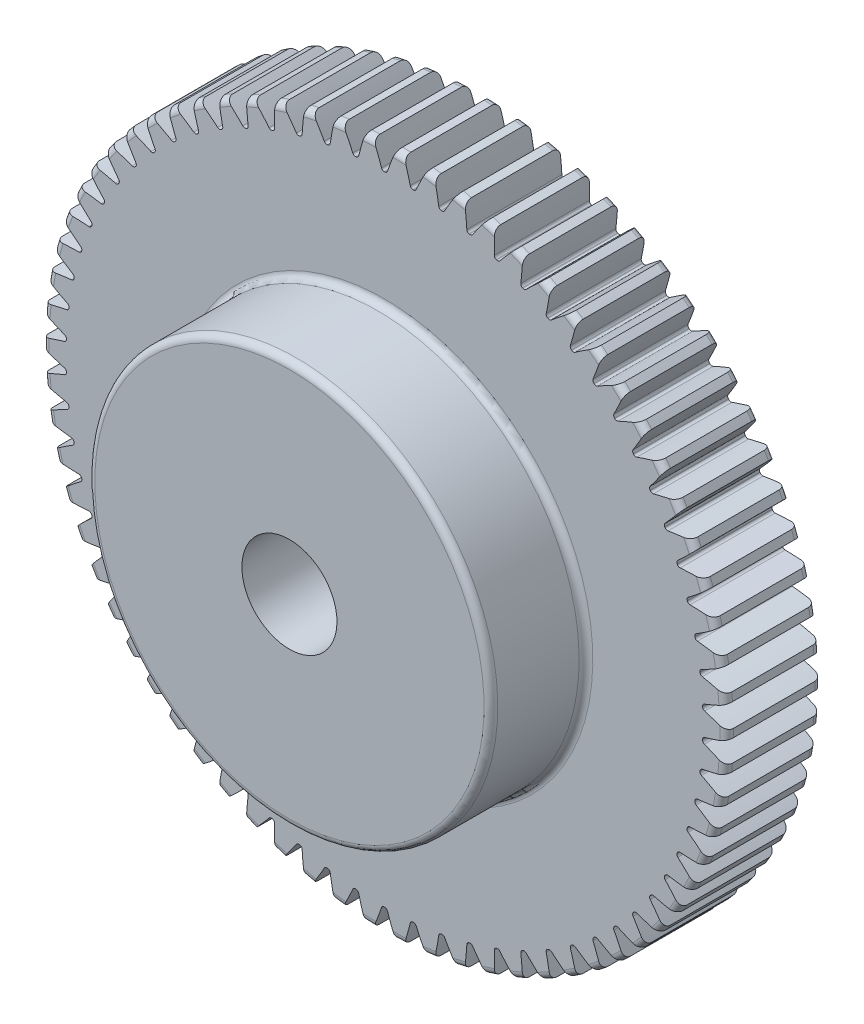
SolidWorks part; units mm, degrees
ref_plane "Front Plane" through (0, 0, 0) normal (0, 0, 1) x (1, 0, 0)
ref_plane "Top Plane" through (0, 0, 0) normal (0, 1, 0) x (1, 0, 0)
ref_plane "Right Plane" through (0, 0, 0) normal (1, 0, 0) x (0, 0, -1)
sketch "Sketch1" plane through (0, 0, 0) normal (0, 0, 1) x (1, 0, 0)
  line L0 (-889, 0) -> (889, 0) construction
  circle A0 centre (0, 0) radius 45.72 construction
  circle A1 centre (0, 0) radius 44.45 construction
  circle A2 centre (0, 0) radius 42.545 construction
  circle A3 centre (0, 0) radius 26.924 construction
  circle A4 centre (0, 0) radius 6.35 construction
  dimension "D2" = 1.27
  dimension "D3" = 3.175
  dimension "D1" = 3.175
sketch "Sketch2" plane through (0, 0, 0) normal (1, 0, 0) x (0, 0, -1)
  line L0 (0, 0) -> (-12.7, 0) construction
  line L1 (-12.7, 0) -> (-25.4, 0) construction
  dimension "Overall Width" = 25.4
  dimension "Face Width" = 12.7
sketch "Sketch4" plane through (0, 0, 0) normal (1, 0, 0) x (0, 0, -1)
  line L0 (-25.4, 6.35) -> (-25.4, 26.924)
  line L1 (-25.4, 26.924) -> (-12.7, 26.924)
  line L2 (-12.7, 26.924) -> (-12.7, 45.72)
  line L3 (-12.7, 45.72) -> (0, 45.72)
  line L4 (0, 45.72) -> (0, 6.35)
  line L5 (-12.7, 26.924) -> (-12.7, 0) construction
  line L6 (0, 45.72) -> (0, -45.72) construction
  line L7 (-12.7, 26.924) -> (0, 26.924) construction
  line L12 (-25.4, 6.35) -> (0, 6.35)
revolve "Revolve1" add sketch "Sketch4" angle 360 about L1
fillet "Fillet2" radius 0.9144 4 edges at (0, 26.924, 25.4) (0, 26.924, 12.7) (0, 45.72, 12.7) (0, 45.72, 0)
sketch "Sketch7" plane through (0, 0, 12.7) normal (0, 0, 1) x (1, 0, 0)
  line L0 (0, 0) -> (0, 45.72) construction
  line L1 (0.9974, 44.4388) -> (1.4871, 45.6958) construction
  line L3 (2.0512, 45.674) -> (1.9942, 44.4052) construction
  line L4 (1.9942, 44.4052) -> (1.9088, 42.5022) construction
  line L5 (0, 0) -> (1.9088, 42.5022) construction
  line L6 (0.9974, 44.4388) -> (0, 0) construction
  line L7 (0.9974, 44.4388) -> (1.0259, 45.7085) construction
  line L8 (0.9974, 44.4388) -> (0, 0) construction
  circle A0 centre (0, 0) radius 45.72 construction
  arc A1 (-0.0358, 42.545) -> (0.0358, 42.545) centre (0, 0) cw
  circle A2 centre (0, 0) radius 42.545 construction
  arc A3 (-0.9974, 44.4388) -> (0.9974, 44.4388) centre (0, 0) cw construction
  circle A4 centre (0, 0) radius 44.45 construction
  arc A5 (2.5931, 45.6464) -> (1.509, 45.6951) centre (0, 0) ccw construction
  arc A6 (0.9974, 44.4388) -> (2.9901, 44.3493) centre (0, 0) cw construction
  arc A7 (-1.509, 45.6951) -> (1.509, 45.6951) centre (0, 0) cw
  arc A8 (0.3963, 42.8017) -> (1.509, 45.6951) centre (42.4151, 28.3026) cw
  arc A9 (-0.3963, 42.8017) -> (-1.509, 45.6951) centre (-42.4151, 28.3026) ccw
  arc A10 (-0.0358, 42.545) -> (-0.3963, 42.8017) centre (-0.0361, 42.926) cw
  arc A11 (0.0358, 42.545) -> (0.3963, 42.8017) centre (0.0361, 42.926) ccw
  point P26 (-0.3082, 42.5439)
  point P29 (0.3082, 42.5439)
  dimension "D4" = 0.381
  dimension "D5" = 44.45
  dimension "D3" = 20
  dimension "D1" = 3.9898
  dimension "D2" = 1.9949
extrude "Cut-Extrude2" cut sketch "Sketch7" against normal through all
pattern_circular "CirPattern1" count 70 over 360 about axis through (0, 0, 25.4) along (0, 0, -1) of "Cut-Extrude2"
fillet "Fillet3" radius 1.016 1 edges at (0, 6.35, 0)
equation "\"D1@Sketch1\"=2.5*(\"Pitch Dia.@Sketch1\"/\"Number of Teeth@Sketch1\")"
equation "\"D1@CirPattern1\"=\"Number of Teeth@Sketch1\""
equation "\"D1@Fillet2\"=\"OD@Sketch1\"*.01"
equation "\"D1@Sketch7\"=3.14159*(\"Pitch Dia.@Sketch1\"/\"Number of Teeth@Sketch1\")"
equation "\"D2@Sketch7\"=\"D1@Sketch7\"/2"
equation "\"D4@Sketch7\"=\"D1@Sketch7\"*.0955"
equation "\"D5@Sketch7\"=\"Pitch Dia.@Sketch1\"/2"
